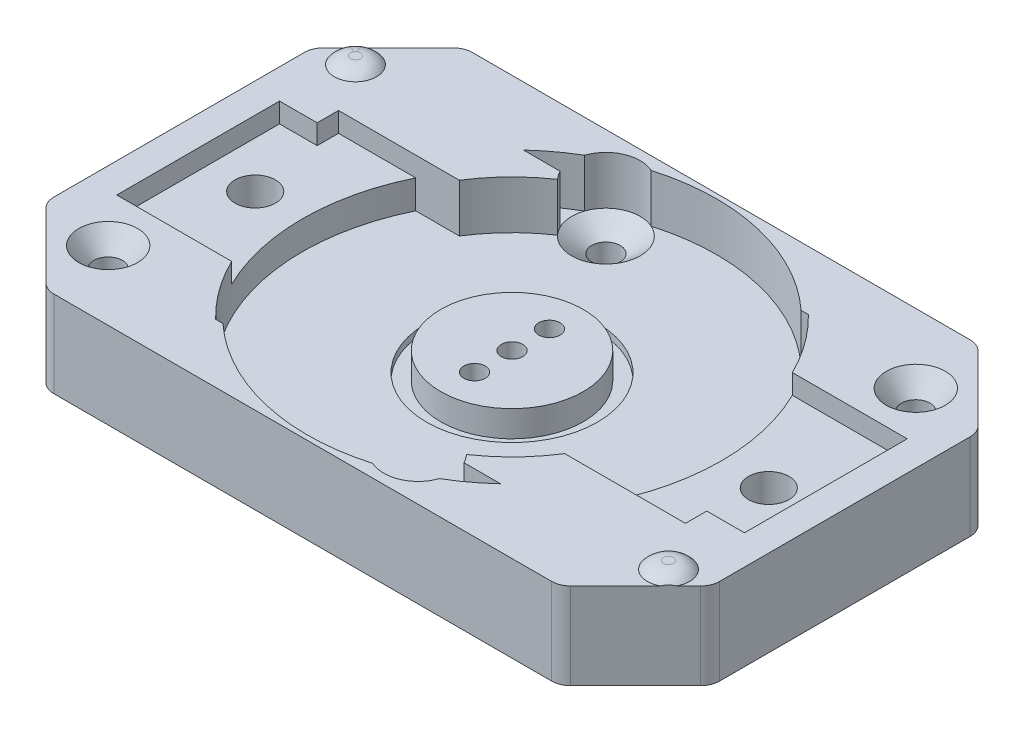
SolidWorks part; units mm, degrees
ref_plane "Front Plane" through (0, 0, 0) normal (0, 0, 1) x (1, 0, 0)
ref_plane "Top Plane" through (0, 0, 0) normal (0, 1, 0) x (1, 0, 0)
ref_plane "Right Plane" through (0, 0, 0) normal (1, 0, 0) x (0, 0, -1)
sketch "Sketch3" plane through (0, 0, 0) normal (0, 1, 0) x (-1, 0, 0)
  line L53 (-27.5858, 21.4142) -> (-34.4142, 14.5858)
  line L55 (-35, 13.1716) -> (-35, -13.1716)
  line L56 (-34.4142, -14.5858) -> (-27.5858, -21.4142)
  line L57 (-26.1716, -22) -> (26.1716, -22)
  line L58 (27.5858, -21.4142) -> (34.4142, -14.5858)
  line L59 (35, -13.1716) -> (35, 13.1716)
  line L60 (34.4142, 14.5858) -> (27.5858, 21.4142)
  line L61 (26.1716, 22) -> (-26.1716, 22)
  line L62 (21.5631, 19) -> (-21.5631, 19)
  line L63 (32, 12.7574) -> (28.5281, 16.2292)
  line L64 (32, -12.7574) -> (32, 12.7574)
  line L65 (28.5281, -16.2292) -> (32, -12.7574)
  line L67 (-21.5631, -19) -> (21.5631, -19)
  line L68 (-32, -12.7574) -> (-28.5281, -16.2292)
  line L69 (-32, 12.7574) -> (-32, -12.7574)
  line L70 (-28.5281, 16.2292) -> (-32, 12.7574)
  line L71 (0, 22) -> (0, -22) construction
  line L73 (-35, 0) -> (35, 0) construction
  circle A2 centre (0, -3.937) radius 1.125
  circle A4 centre (0, 3.937) radius 1.125
  circle A6 centre (25, -17.5) radius 1.5
  arc A7 (-34.4142, 14.5858) -> (-35, 13.1716) centre (-33, 13.1716) ccw
  circle A8 centre (0, 0) radius 7.493
  arc A10 (-35, -13.1716) -> (-34.4142, -14.5858) centre (-33, -13.1716) ccw
  circle A18 centre (0, 0) radius 1.125
  arc A19 (-27.5858, -21.4142) -> (-26.1716, -22) centre (-26.1716, -20) ccw
  arc A47 (26.1716, -22) -> (27.5858, -21.4142) centre (26.1716, -20) ccw
  arc A48 (34.4142, -14.5858) -> (35, -13.1716) centre (33, -13.1716) ccw
  arc A49 (35, 13.1716) -> (34.4142, 14.5858) centre (33, 13.1716) ccw
  arc A50 (27.5858, 21.4142) -> (26.1716, 22) centre (26.1716, 20) ccw
  arc A51 (-26.1716, 22) -> (-27.5858, 21.4142) centre (-26.1716, 20) ccw
  arc A52 (-28.5281, 16.2292) -> (-21.5631, 19) centre (-25, 17.5) ccw
  arc A53 (21.5631, 19) -> (28.5281, 16.2292) centre (25, 17.5) ccw
  arc A54 (28.5281, -16.2292) -> (21.5631, -19) centre (25, -17.5) ccw
  arc A55 (-21.5631, -19) -> (-28.5281, -16.2292) centre (-25, -17.5) ccw
  circle A56 centre (25, 17.5) radius 1.5
  circle A57 centre (-25, 17.5) radius 1.5
  circle A58 centre (-25, -17.5) radius 1.5
  point P0 (0, 0)
  dimension "D1" = 14.986
  dimension "D2" = 2.25
  dimension "D5" = 3
  dimension "D3" = 7.874
extrude "Boss-Extrude1" add sketch "Sketch3" along normal blind 4 contours A8 | A8 A18 A2 A4 | L61 A51 L53 A7 L55 A10 L56 A19 L57 A47 L58 A48 L59 A49 L60 A50 A58 A57 A56 A6 L67 A55 L68 L69 L70 A52 L62 A53 L63 L64 L65 A54 | A58 | A6 | A56 | A57 region at (26.6205, 0, 21.0839) region at (-23.3387, 0, 13.324) region at (-25, 0, -17.5) region at (7.2811, 0, 0) region at (-25, 0, 17.5) region at (25, 0, 17.5) region at (25, 0, -17.5)
sketch "Sketch2" plane through (0, 4, 0) normal (0, 1, 0) x (1, 0, 0)
  line L0 (8.6989, -15.799) -> (22.987, -15.799)
  line L2 (-27.9195, 7.436) -> (-27.9195, 9.678)
  line L3 (-27.9195, 9.678) -> (-15.2189, 9.678)
  line L4 (27.9195, -9.678) -> (27.9195, -7.436)
  line L5 (15.2189, -9.678) -> (27.9195, -9.678)
  line L7 (-22.987, -15.799) -> (-15.3666, -15.799)
  line L9 (-22.987, 15.799) -> (-8.6989, 15.799)
  line L11 (15.3666, 15.799) -> (22.987, 15.799)
  line L12 (-31.8805, -9.678) -> (-19.8009, -9.678)
  line L13 (-31.8805, -9.678) -> (-31.8805, 7.436)
  line L14 (-31.8805, 7.436) -> (-27.9195, 7.436)
  line L15 (31.8805, 9.678) -> (19.8009, 9.678)
  line L16 (31.8805, 9.678) -> (31.8805, -7.436)
  line L17 (31.8805, -7.436) -> (27.9195, -7.436)
  line L19 (-22.987, -15.799) -> (-22.987, -22)
  line L21 (22.987, -15.799) -> (22.987, -22)
  line L25 (-31.8805, 0) -> (31.8805, 0) construction
  line L26 (22.987, 15.799) -> (22.987, 22)
  line L28 (-22.987, 15.799) -> (-22.987, 22)
  line L33 (-26.1716, -22) -> (26.1716, -22)
  line L34 (27.5858, -21.4142) -> (34.4142, -14.5858)
  line L35 (35, -13.1716) -> (35, 13.1716)
  line L36 (34.4142, 14.5858) -> (27.5858, 21.4142)
  line L37 (26.1716, 22) -> (-26.1716, 22)
  line L38 (-27.5858, 21.4142) -> (-34.4142, 14.5858)
  line L40 (-35, 13.1716) -> (-35, -13.1716)
  line L41 (-34.4142, -14.5858) -> (-27.5858, -21.4142)
  line L42 (-26.1716, -22) -> (26.1716, -22)
  line L43 (27.5858, -21.4142) -> (34.4142, -14.5858)
  line L44 (35, -13.1716) -> (35, 13.1716)
  line L46 (34.4142, 14.5858) -> (27.5858, 21.4142)
  line L48 (26.1716, 22) -> (-26.1716, 22)
  line L49 (-27.5858, 21.4142) -> (-34.4142, 14.5858)
  line L51 (-35, 13.1716) -> (-35, -13.1716)
  line L53 (-34.4142, -14.5858) -> (-27.5858, -21.4142)
  arc A0 (-19.8009, -9.678) -> (-15.3666, -15.799) centre (0, 0) ccw
  arc A1 (8.6989, -15.799) -> (15.2189, -9.678) centre (0, 0) ccw
  arc A2 (-8.6989, 15.799) -> (-15.2189, 9.678) centre (0, 0) ccw
  arc A3 (19.8009, 9.678) -> (15.3666, 15.799) centre (0, 0) ccw
  circle A4 centre (-27, 0) radius 2.125
  circle A5 centre (27, 0) radius 2.125
  arc A6 (-19.8009, -9.678) -> (-19.8009, 9.678) centre (0, 0) cw
  arc A7 (19.8009, 9.678) -> (19.8009, -9.678) centre (0, 0) cw
  arc A22 (26.1716, -22) -> (27.5858, -21.4142) centre (26.1716, -20) ccw
  arc A24 (34.4142, -14.5858) -> (35, -13.1716) centre (33, -13.1716) ccw
  arc A25 (35, 13.1716) -> (34.4142, 14.5858) centre (33, 13.1716) ccw
  arc A27 (27.5858, 21.4142) -> (26.1716, 22) centre (26.1716, 20) ccw
  arc A28 (-26.1716, 22) -> (-27.5858, 21.4142) centre (-26.1716, 20) ccw
  arc A42 (-34.4142, 14.5858) -> (-35, 13.1716) centre (-33, 13.1716) ccw
  arc A43 (-35, -13.1716) -> (-34.4142, -14.5858) centre (-33, -13.1716) ccw
  arc A56 (-27.5858, -21.4142) -> (-26.1716, -22) centre (-26.1716, -20) ccw
  arc A57 (26.1716, -22) -> (27.5858, -21.4142) centre (26.1716, -20) ccw
  arc A58 (34.4142, -14.5858) -> (35, -13.1716) centre (33, -13.1716) ccw
  arc A59 (35, 13.1716) -> (34.4142, 14.5858) centre (33, 13.1716) ccw
  arc A60 (27.5858, 21.4142) -> (26.1716, 22) centre (26.1716, 20) ccw
  arc A61 (-26.1716, 22) -> (-27.5858, 21.4142) centre (-26.1716, 20) ccw
  arc A62 (-34.4142, 14.5858) -> (-35, 13.1716) centre (-33, 13.1716) ccw
  arc A63 (-35, -13.1716) -> (-34.4142, -14.5858) centre (-33, -13.1716) ccw
  arc A64 (-27.5858, -21.4142) -> (-26.1716, -22) centre (-26.1716, -20) ccw
  dimension "D1" = 36.071
  dimension "D2" = 44.079
  dimension "D8" = 4.25
  dimension "D3" = 55.839
  dimension "D4" = 63.761
  dimension "D5" = 19.356
  dimension "D6" = 31.598
  dimension "D7" = 54
  dimension "D9" = 2.242
  dimension "D10" = 2.242
  dimension "D11" = 0
extrude "Boss-Extrude2" add sketch "Sketch2" along normal blind 3 contours L15 A7 L5 L4 L17 L16 A5 | L12 A6 L3 L2 L14 L13 A4 | L25 L13 L12 A6 A4 | A7 L25 A5 L16 L15 region at (26.197, 4, 4.9802) region at (26.5424, 4, -5.3138) region at (-26.5424, 4, 5.3138) region at (-26.197, 4, -4.9802)
extrude "Boss-Extrude3" add sketch "Sketch2<4>" along normal blind 5.08 contours A3 L15 L16 L17 L4 L5 A1 L0 L11 | A2 L9 L7 A0 L12 L13 L14 L2 L3 region at (12.6952, 4, 13.5228) region at (-24.5793, 4, 21.4874)
sketch "Sketch2<4>" plane through (0, 4, 0) normal (0, 1, 0) x (1, 0, 0) same geometry as "Sketch2"
sketch "Sketch4" plane through (0, 4, 0) normal (0, 1, 0) x (1, 0, 0)
  circle A0 centre (0, 0) radius 7.493
  circle A1 centre (0, 0) radius 9
  circle A2 centre (0, 3.937) radius 1.125
  circle A3 centre (0, 0) radius 1.125
  circle A4 centre (0, -3.937) radius 1.125
  dimension "D1" = 14.986
  dimension "D2" = 18
extrude "Boss-Extrude4" add sketch "Sketch4" along normal blind 2.02 contours A0 A4 A3 A2 region at (-7.2811, 4, 0)
extrude "Cut-Extrude1" cut sketch "Sketch4<3>" against normal blind 0.728 contours A1 A0 region at (-8.7454, 4, 0)
sketch "Sketch4<3>" plane through (0, 4, 0) normal (0, 1, 0) x (1, 0, 0) same geometry as "Sketch4"
sketch "Sketch7" plane through (0, 7, 0) normal (0, 1, 0) x (1, 0, 0)
  circle A0 centre (-27, 0) radius 2.125
  circle A1 centre (27, 0) radius 2.125
extrude "Cut-Extrude3" cut sketch "Sketch7" against normal through all
sketch "Sketch8" plane through (0, 0, 0) normal (0, -1, 0) x (1, 0, 0)
  circle A0 centre (-27.7296, 14.7296) radius 1.5
  circle A1 centre (7.5, 17.375) radius 1.5
  circle A2 centre (27.7296, -14.7296) radius 1.5
  circle A3 centre (-7.5, -17.375) radius 1.5
  dimension "D1" = 3
extrude "Cut-Extrude4" cut sketch "Sketch8" against normal through all
sketch "Sketch10" plane through (0, 4, 0) normal (0, 1, 0) x (1, 0, 0)
  circle A0 centre (7.5, -17.375) radius 3.6
  circle A1 centre (-7.5, 17.375) radius 3.6
  dimension "D1" = 7.2
extrude "Cut-Extrude6" cut sketch "Sketch10" along normal through all
chamfer "Chamfer1" distance 2.1 distance2 1.6 4 edges at (-27.7296, 9.08, 13.2296) (-7.5, 4, -15.875) (7.5, 4, 18.875) (27.7296, 9.08, -16.2296) first distance on face at (-27.7296, 9.08, 13.2296) first distance on face at (0, 4, 9) first distance on face at (27.7296, 9.08, -16.2296)
sketch "Sketch11" plane through (0, 9.08, 0) normal (0, 1, 0) x (1, 0, 0)
  line L0 (0, 0) -> (0, -22) construction
  line L1 (31.2095, -14.7515) -> (-31.2095, -14.7515)
  line L2 (31.2095, -14.7515) -> (31.2095, 14.7515)
  line L3 (31.2095, 14.7515) -> (-31.2095, 14.7515)
  line L4 (-31.2095, -14.7515) -> (-31.2095, 14.7515)
  line L5 (-22.987, -22) -> (22.987, -22) construction
  circle A0 centre (31.2095, -14.7515) radius 2.2255
  circle A1 centre (-31.2095, 14.7515) radius 2.2255
  point P11 (-31.2095, 0)
  point P12 (0, -14.7515)
  line M11 (27.5858, -21.4142) -> (34.4142, -14.5858)
  dimension "D1" = 4.451
  dimension "D2" = 29.503
  dimension "D3" = 62.419
extrude "Boss-Extrude5" add sketch "Sketch11" along normal blind 0.8 contours L3 A1 L4 | L4 A1 L3 | L2 A0 L1 | A0 L2 L1 M11 region at (31.5181, 9.08, 15.0601) region at (30.265, 9.08, 13.807) region at (-31.5243, 9.08, -15.0663) region at (-30.265, 9.08, -13.807)
fillet "Fillet1" radius 2.2 2 edges at (-31.2095, 9.88, -12.526) (29.6358, 9.88, 13.1778)
sketch "Sketch12" plane through (0, 4, 0) normal (0, 1, 0) x (1, 0, 0)
  line L0 (-22.987, -15.799) -> (-14.6001, -15.799)
  line L1 (-22.987, -15.799) -> (-22.987, -22)
  line L2 (-22.987, -22) -> (22.987, -22)
  line L3 (22.987, -22) -> (22.987, -15.799)
  line L4 (22.987, -15.799) -> (14.6001, -15.799)
  line L5 (10.7367, -15.799) -> (22.987, -15.799) construction
  line L6 (-21.5121, 0) -> (21.5121, 0) construction
  line L7 (22.987, 15.799) -> (14.6001, 15.799)
  line L8 (22.987, 22) -> (22.987, 15.799)
  line L9 (-22.987, 15.799) -> (-22.987, 22)
  line L10 (-22.987, 22) -> (22.987, 22)
  line L11 (-22.987, 15.799) -> (-14.6001, 15.799)
  circle A0 centre (0, 0) radius 21.5121
  line M2 (-22.987, 15.799) -> (-10.7367, 15.799)
  arc M3 (-10.7367, 15.799) -> (-10.1329, 14.9199) centre (-7.5, 17.375) cw
  line M7 (-15.3666, -15.799) -> (-22.987, -15.799)
  line M8 (-22.987, -15.799) -> (-22.987, -22)
  line M9 (-22.987, -22) -> (22.987, -22)
  line M10 (22.987, -22) -> (22.987, -15.799)
  line M11 (22.987, -15.799) -> (10.7367, -15.799)
  arc M12 (10.7367, -15.799) -> (10.1329, -14.9199) centre (7.5, -17.375) cw
  line M16 (15.3666, 15.799) -> (22.987, 15.799)
  line M17 (22.987, 15.799) -> (22.987, 22)
  line M18 (22.987, 22) -> (-22.987, 22)
  line M19 (-22.987, 22) -> (-22.987, 15.799)
  dimension "D1" = 43.0242
extrude "Boss-Extrude6" add sketch "Sketch12" along normal up to surface (5.08 mm away) contours A0 L0 M12 M7 M8 M9 M10 M11 | A0 L7 M16 M17 M18 M19 M2 M3 region at (-19.1768, 4, 16.2629) region at (-18.7935, 4, -16.2629) up to face at (-27.7296, 9.08, 17.8296)
